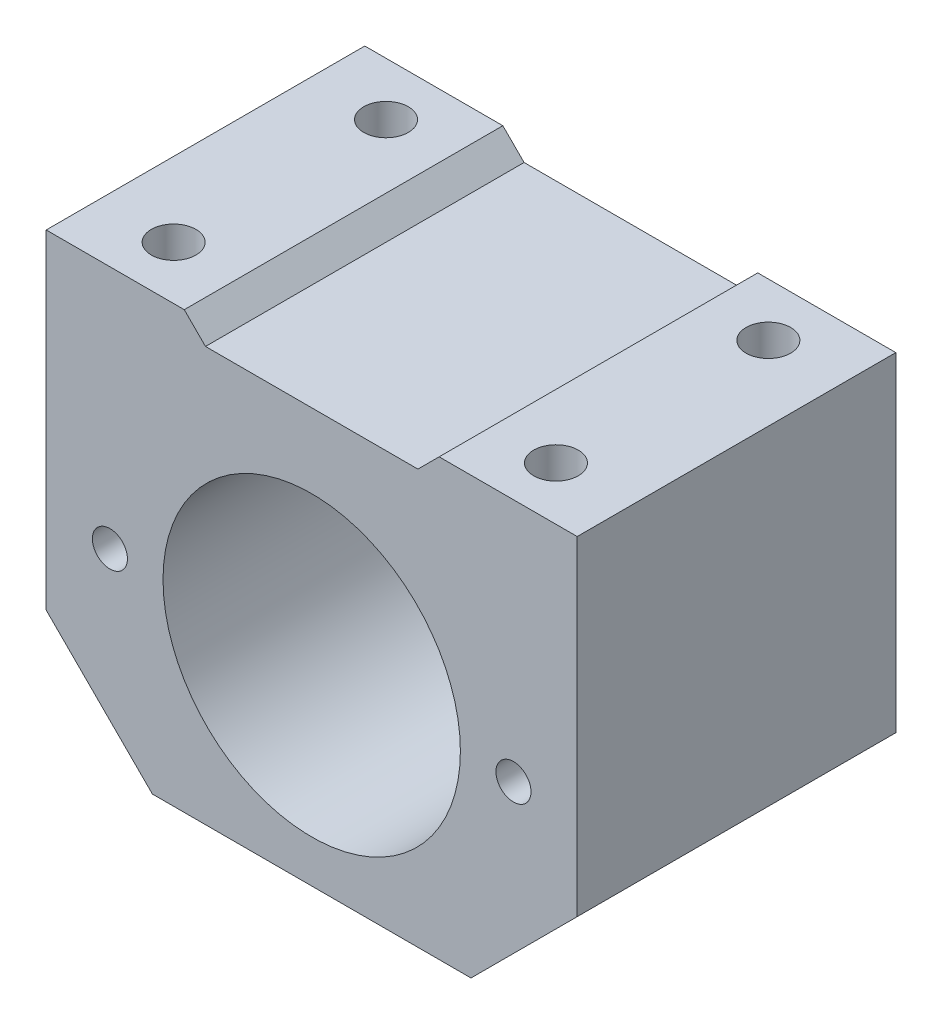
SolidWorks part; units mm, degrees
material "6061 Alloy"
ref_plane "Ön Düzlem" through (0, 0, 0) normal (0, 0, 1) x (1, 0, 0)
ref_plane "Üst Düzlem" through (0, 0, 0) normal (0, 1, 0) x (1, 0, 0)
ref_plane "Sağ Düzlem" through (0, 0, 0) normal (1, 0, 0) x (0, 0, -1)
sketch "Sketch1" plane through (0, 0, 0) normal (0, 0, 1) x (1, 0, 0)
  line L1 (-25, 20.5) -> (25, 20.5)
  line L2 (-25, 20.5) -> (-25, -20.5)
  line L3 (-25, -20.5) -> (25, -20.5)
  line L4 (25, 20.5) -> (25, -20.5)
  line L5 (-25, 20.5) -> (25, -20.5) construction
  line L6 (-25, -20.5) -> (25, 20.5) construction
  point P0 (0, 0)
  dimension "D1" = 41
  dimension "D2" = 50
extrude "Boss-Extrude1" add sketch "Sketch1" along normal blind 30
sketch "Sketch8" plane through (0, 0, 30) normal (0, 0, 1) x (1, 0, 0)
  line L0 (25, 20.5) -> (-25, 20.5) construction
  line L2 (-12, 18.5) -> (12, 18.5)
  line L3 (-12, 18.5) -> (-12, 22.5)
  line L4 (-12, 22.5) -> (12, 22.5)
  line L5 (12, 18.5) -> (12, 22.5)
  line L6 (-12, 18.5) -> (12, 22.5) construction
  line L7 (-12, 22.5) -> (12, 18.5) construction
  circle A0 centre (0, -2.5) radius 14
  point P2 (0, 20.5)
  point P6 (0, 20.5)
  dimension "D1" = 28
  dimension "D2" = 23
  dimension "D3" = 24
  dimension "D4" = 4
extrude "Cut-Extrude1" cut sketch "Sketch8" against normal through all
hole_wizard "Tap Drill for M4 Tap1" positions "Sketch3" profile "Sketch4" hole size "M4" standard "ISO" end condition through all
sketch "Sketch3" plane through (0, 0, 30) normal (0, 0, 1) x (1, 0, 0)
  line L0 (-12, 20.5) -> (-25, 20.5) construction
  line L1 (0, 0) -> (0, -24.7837) construction
  point P13 (19, -2.5)
  point P15 (-19, -2.5)
  dimension "D1" = 38
  dimension "D2" = 19
  dimension "D3" = 23
sketch "Sketch4" plane through (19, -2.5, 30) normal (1, 0, 0) x (0, -1, 0)
  line L0 (0, 0) -> (0, 30)
  line L1 (0, 30) -> (1.65, 30)
  line L2 (1.65, 30) -> (1.65, 0)
  line L5 (1.65, 0) -> (0, 0)
  line L11 (0, -6.35) -> (0, 107.95) construction
  dimension "Thru Hole Dia." = 3.3
  dimension "Thru Hole Depth" = 30
sketch "Sketch5" plane through (0, 20.5, 0) normal (0, 1, 0) x (1, 0, 0)
  line L0 (0, 0) -> (0, -30) construction
  line L2 (25, 0) -> (12, 0) construction
  line L3 (-18, -25) -> (18, -25)
  line L4 (-18, -25) -> (-18, -5)
  line L5 (-18, -5) -> (18, -5)
  line L6 (18, -25) -> (18, -5)
  line L7 (-18, -25) -> (18, -5) construction
  line L8 (-18, -5) -> (18, -25) construction
  line L9 (-12, 0) -> (12, 0) construction
  line L10 (-12, -30) -> (12, -30) construction
  point P8 (0, -15)
  dimension "D1" = 36
  dimension "D2" = 20
  dimension "D3" = 15
hole_wizard "Tap Drill for M5 Tap2" positions "Sketch9" profile "Sketch10" hole size "M5" standard "ISO"
sketch "Sketch9" plane through (0, 20.5, 0) normal (0, 1, 0) x (1, 0, 0)
  point P0 (-18, -25)
  point P3 (-18, -5)
  point P6 (18, -5)
  point P9 (18, -25)
sketch "Sketch10" plane through (-18, 20.5, 25) normal (1, 0, 0) x (0, 0, 1)
  line L0 (0, 0) -> (0, 16.2618)
  line L1 (0, 16.2618) -> (2.1, 15)
  line L2 (2.1, 15) -> (2.1, 0)
  line L5 (2.1, 0) -> (0, 0)
  line L10 (0, 16.2618) -> (-2.1, 15) construction
  line L11 (0, -6.35) -> (0, 107.95) construction
  dimension "Hole Dia." = 4.2
  dimension "Hole Depth" = 15
  dimension "Drill Angle" = 118
chamfer "Chamfer1" distance 2 angle 45 2 edges at (12, 18.5, 15) (-12, 18.5, 15)
chamfer "Chamfer2" distance 10 angle 45 2 edges at (25, -20.5, 15) (-25, -20.5, 15)
